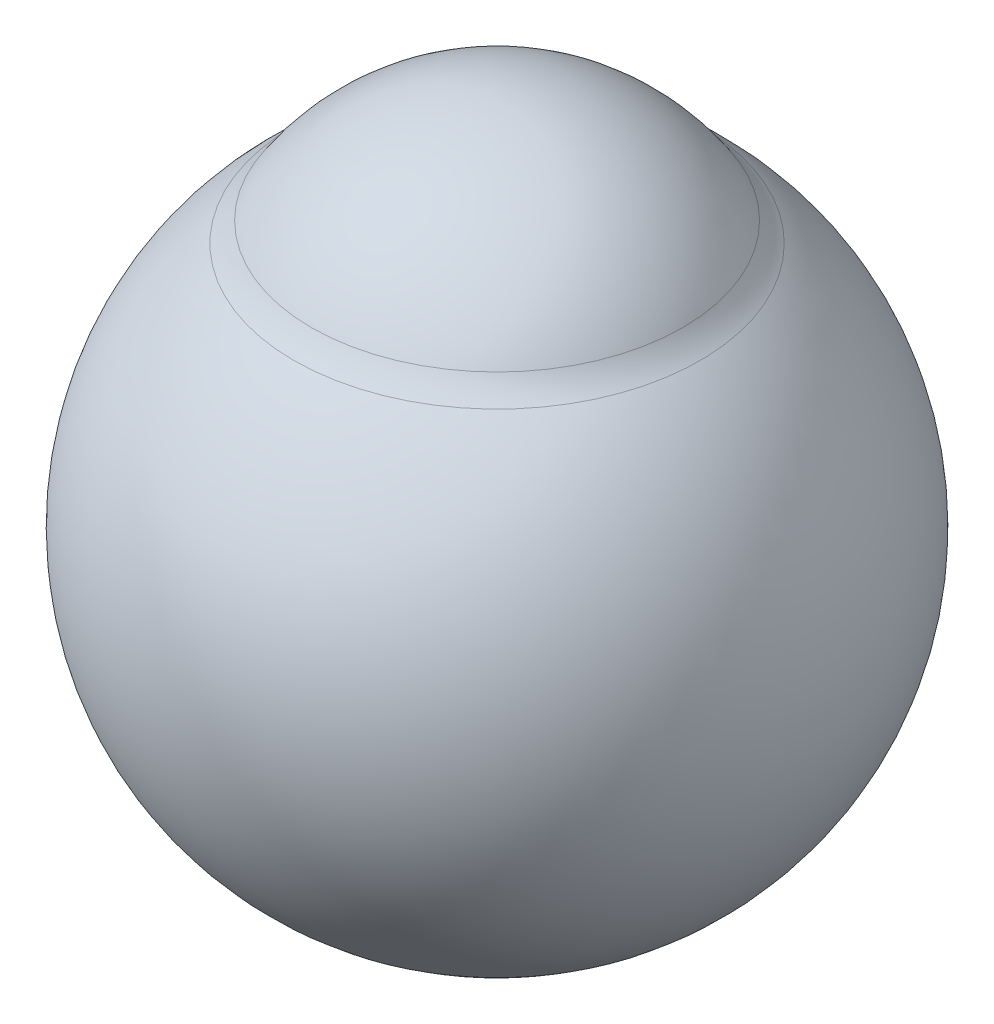
SolidWorks part; units mm, degrees
ref_plane "Front" through (0, 0, 0) normal (0, 0, 1) x (1, 0, 0)
ref_plane "Top" through (0, 0, 0) normal (0, 1, 0) x (1, 0, 0)
ref_plane "Right" through (0, 0, 0) normal (1, 0, 0) x (0, 0, -1)
sketch "Sketch6" plane through (0, 0, 0) normal (0, 0, 1) x (1, 0, 0)
  line L0 (0, 60.2442) -> (0, -60.6715) construction
  line L1 (5.5482, 4.3361) -> (5.8861, 4.08)
  line L2 (1.5, 4.18) -> (5.4653, 4.18)
  line L3 (1.5, 4.18) -> (1.5, 4.08)
  line L4 (1.5, 4.08) -> (5.4929, 4.08)
  line L5 (5.4929, 4.08) -> (5.8861, 4.08)
  line L6 (5.8861, 4.08) -> (6.4597, 3.6926)
  line L7 (0, 7.8) -> (0, 7.28)
  line L8 (0, 4.08) -> (0, 0.38)
  line L9 (0, -16.2) -> (0, -16.52)
  line L10 (5.5482, 4.3361) -> (5.8861, 4.08)
  line L11 (5.4929, 4.08) -> (5.8861, 4.08)
  arc A0 (6.5776, 4.1923) -> (0, 7.8) centre (0, 0) ccw
  arc A1 (5.5482, 4.3361) -> (0, 7.28) centre (0, 0.58) ccw
  arc A2 (5.6645, 3.7773) -> (5.4929, 4.08) centre (5.4929, 3.88) ccw
  arc A3 (4.705, 2.904) -> (0, 4.08) centre (0, -5.92) ccw
  arc A4 (0, 0.38) -> (4.7466, 2.7099) centre (0, 6.38) ccw
  arc A5 (0, -16.52) -> (7.1968, 3.4919) centre (0, -5.22) ccw
  arc A8 (7.1968, 3.4919) -> (6.5776, 4.1923) centre (9.1074, 5.8048) cw
  arc A9 (5.4653, 4.18) -> (5.5482, 4.3361) centre (5.4653, 4.28) ccw
  arc A10 (4.7466, 2.7099) -> (4.705, 2.904) centre (4.6439, 2.7894) ccw
  arc A12 (0, -16.2) -> (6.4597, 3.6926) centre (0, -5.2049) ccw
  spline S0 degree 3 poles (5.5482, 4.3361) (5.403, 5.0449) (6.0513, 4.9263) (6.5209, 4.28) knots 0 0 0 0 1 1 1 1
  spline S1 degree 3 poles (5.6645, 3.7773) (5.528, 3.5492) (5.4172, 2.8544) (6.9838, 2.5219) (8.0807, 1.9174) (8.5323, 1.73) knots 0.065551 0.065551 0.065551 0.065551 0.226972 0.688222 1 1 1 1
  dimension "D9" = 0.52
  dimension "D13" = 3.2
  dimension "D14" = 3
  dimension "D15" = 16.58
  dimension "D12" = 7.8
  dimension "D16" = 6.7
  dimension "D17" = 10
  dimension "D18" = 6
  dimension "D19" = 10.9951
  dimension "D2" = 0.2
  dimension "D10" = 1.5
  dimension "D11" = 3.7
revolve "lens" add sketch "Sketch6" angle 360 about L0 region at (1.8601, 2.3263, 0)
revolve "iris" add sketch "Sketch6<7>" angle 360 about L0 region at (3.7294, 4.1331, 0)
sketch "Sketch6<7>" plane through (0, 0, 0) normal (0, 0, 1) x (1, 0, 0) same geometry as "Sketch6"
revolve "ciliary body" add sketch "Sketch6<12>" angle 360 about L0 region at (6.6808, 2.995, 0)
sketch "Sketch6<12>" plane through (0, 0, 0) normal (0, 0, 1) x (1, 0, 0) same geometry as "Sketch6"
revolve "sclera" add sketch "Sketch6<13>" angle 360 about L0 region at (5.8444, 4.5588, 0)
sketch "Sketch6<13>" plane through (0, 0, 0) normal (0, 0, 1) x (1, 0, 0) same geometry as "Sketch6"
revolve "cornea" add sketch "Sketch6<14>" angle 360 about L0 region at (3.3, 6.4623, 0)
sketch "Sketch6<14>" plane through (0, 0, 0) normal (0, 0, 1) x (1, 0, 0) same geometry as "Sketch6"
